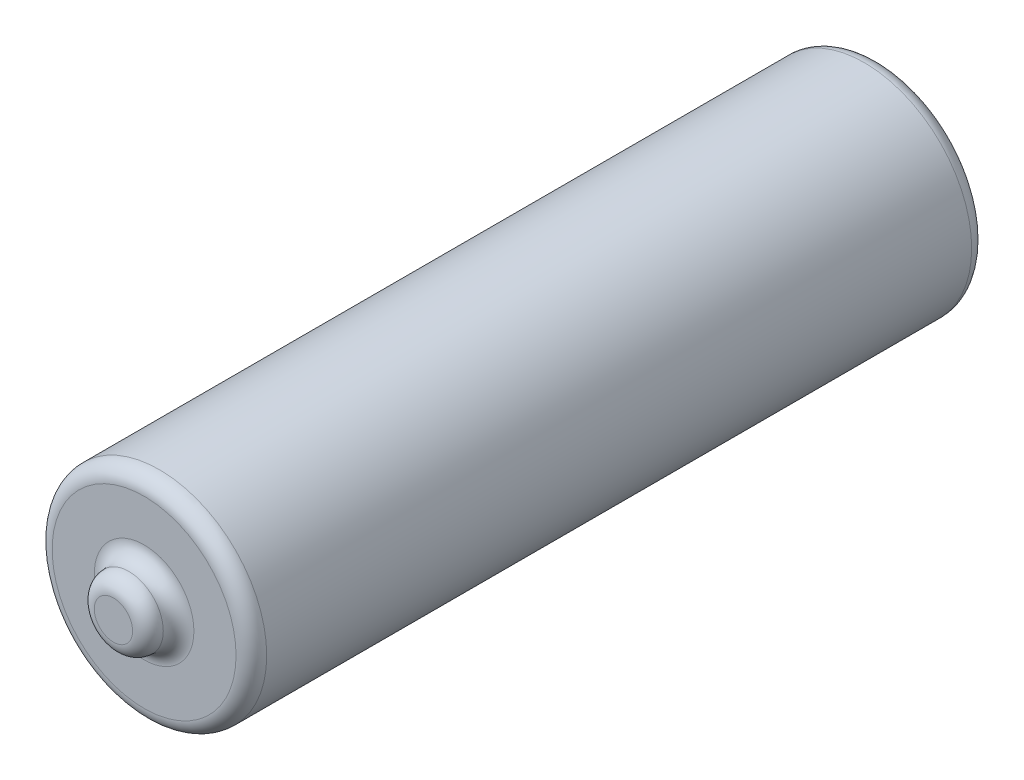
SolidWorks part; units mm, degrees
ref_plane "Front Plane" through (0, 0, 0) normal (0, 0, 1) x (1, 0, 0)
ref_plane "Top Plane" through (0, 0, 0) normal (0, 1, 0) x (1, 0, 0)
ref_plane "Right Plane" through (0, 0, 0) normal (1, 0, 0) x (0, 0, -1)
sketch "Sketch1" plane through (0, 0, 0) normal (0, 0, 1) x (1, 0, 0)
  circle A0 centre (0, 0) radius 7
  dimension "D1" = 14
extrude "Boss-Extrude1" add sketch "Sketch1" along normal blind 48
fillet "Fillet1" radius 1 2 edges at (7, 0, 0) (7, 0, 48)
sketch "Sketch2" plane through (0, 0, 48) normal (0, 0, 1) x (1, 0, 0)
  circle A0 centre (0, 0) radius 2.25
  dimension "D1" = 4.5
extrude "Boss-Extrude2" add sketch "Sketch2" along normal blind 2
fillet "Fillet2" radius 1 2 edges at (2.25, 0, 50) (2.25, 0, 48)
sketch "Sketch3" plane through (0, 0, 0) normal (0, 0, -1) x (-1, 0, 0)
  circle A0 centre (0, 0) radius 3.7609
  circle A1 centre (0, 0) radius 2.7573
extrude "Cut-Extrude1" cut sketch "Sketch3" against normal blind 1
fillet "Fillet3" radius 0.5 3 edges at (-2.7573, 0, 0) (-3.7609, 0, 1) (-2.7573, 0, 1)
